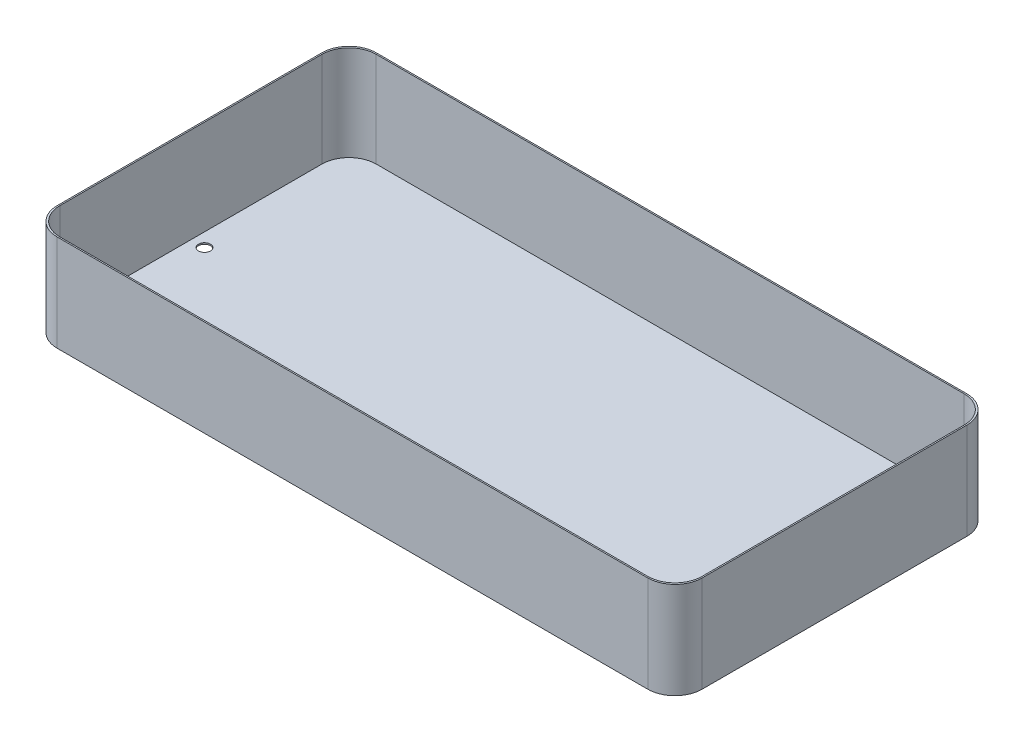
SolidWorks part; units mm, degrees
ref_plane "Front Plane" through (0, 0, 0) normal (0, 0, 1) x (1, 0, 0)
ref_plane "Top Plane" through (0, 0, 0) normal (0, 1, 0) x (1, 0, 0)
ref_plane "Right Plane" through (0, 0, 0) normal (1, 0, 0) x (0, 0, -1)
sketch "Sketch1" plane through (0, 0, 0) normal (0, 1, 0) x (1, 0, 0)
  line L1 (-603.25, -298.45) -> (603.25, -298.45)
  line L2 (-603.25, -298.45) -> (-603.25, 298.45)
  line L3 (-603.25, 298.45) -> (603.25, 298.45)
  line L4 (603.25, -298.45) -> (603.25, 298.45)
  line L5 (-603.25, -298.45) -> (603.25, 298.45) construction
  line L6 (-603.25, 298.45) -> (603.25, -298.45) construction
  line L7 (-600.71, -295.91) -> (600.71, -295.91)
  line L8 (-600.71, -295.91) -> (-600.71, 295.91)
  line L9 (-600.71, 295.91) -> (600.71, 295.91)
  line L10 (600.71, -295.91) -> (600.71, 295.91)
  line L11 (-600.71, -295.91) -> (600.71, 295.91) construction
  line L12 (-600.71, 295.91) -> (600.71, -295.91) construction
  point P0 (0, 0)
  point P6 (0, 0)
  dimension "D1" = 596.9
  dimension "D2" = 1206.5
  dimension "D3" = 2.54
  dimension "D4" = 2.54
extrude "Boss-Extrude1" add sketch "Sketch1" along normal blind 177.8
sketch "Sketch2" plane through (0, 0, 0) normal (0, -1, 0) x (1, 0, 0)
  line L1 (603.25, 298.45) -> (-603.25, 298.45)
  line L2 (603.25, 298.45) -> (603.25, -298.45)
  line L3 (603.25, -298.45) -> (-603.25, -298.45)
  line L4 (-603.25, 298.45) -> (-603.25, -298.45)
  line L5 (603.25, 298.45) -> (-603.25, -298.45) construction
  line L6 (603.25, -298.45) -> (-603.25, 298.45) construction
  point P0 (0, 0)
extrude "Boss-Extrude2" add sketch "Sketch2" along normal blind 2.54
fillet "Fillet1" radius 50.8 8 edges at (600.71, 88.9, 295.91) (-600.71, 88.9, 295.91) (-600.71, 88.9, -295.91) (600.71, 88.9, -295.91) (603.25, 87.63, -298.45) (603.25, 87.63, 298.45) (-603.25, 87.63, 298.45) (-603.25, 87.63, -298.45)
hole_wizard "7/8 (0.875) Diameter Hole1" positions "Sketch3" profile "Sketch4" hole size "7/8" standard "ANSI Inch" end condition up to next
sketch "Sketch3" plane through (0, 0, 0) normal (0, 1, 0) x (1, 0, 0)
  line L0 (-594.9868, 0) -> (600.71, 0) construction
  line L1 (600.71, -245.11) -> (600.71, 245.11) construction
  line L2 (-600.71, 245.11) -> (-600.71, -245.11) construction
  line L3 (600.71, -245.11) -> (600.71, 245.11) construction
  point P6 (-575.31, 0)
  point P8 (575.31, 0)
  dimension "D1" = 25.4
  dimension "D2" = 25.4
sketch "Sketch4" plane through (575.31, 0, 0) normal (1, 0, 0) x (0, 0, 1)
  line L0 (0, 0) -> (0, 2.54)
  line L1 (0, 2.54) -> (11.1125, 2.54)
  line L2 (11.1125, 2.54) -> (11.1125, 0)
  line L5 (11.1125, 0) -> (0, 0)
  line L11 (0, -6.35) -> (0, 107.95) construction
  dimension "Thru Hole Dia." = 22.225
  dimension "Thru Hole Depth" = 2.54
